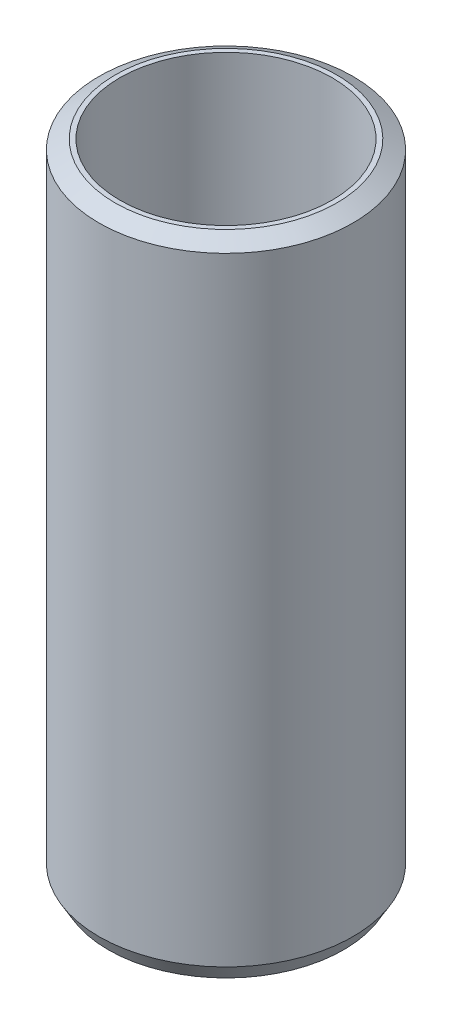
SolidWorks part; units mm, degrees
ref_plane "Front Plane" through (0, 0, 0) normal (0, 0, 1) x (1, 0, 0)
ref_plane "Top Plane" through (0, 0, 0) normal (0, 1, 0) x (1, 0, 0)
ref_plane "Right Plane" through (0, 0, 0) normal (1, 0, 0) x (0, 0, -1)
sketch "Sketch1" plane through (0, 0, 0) normal (0, 1, 0) x (1, 0, 0)
  circle A0 centre (0, 0) radius 55
  dimension "SHAFT_OD" = 110
extrude "Boss-Extrude1" add sketch "Sketch1" along normal blind 278.6061
sketch "Sketch2" plane through (0, 0, 0) normal (0, 1, 0) x (1, 0, 0)
  circle A0 centre (0, 0) radius 45.9566
  dimension "BORE_D" = 91.9132
extrude "Cut-Extrude1" cut sketch "Sketch2" along normal through all
chamfer "Chamfer1" distance 4.0302 angle 60 2 edges at (0, 278.6061, 55) (0, 0, 55) first distance on face at (0, 278.6061, 55) first distance on face at (0, 0, 45.9566)
